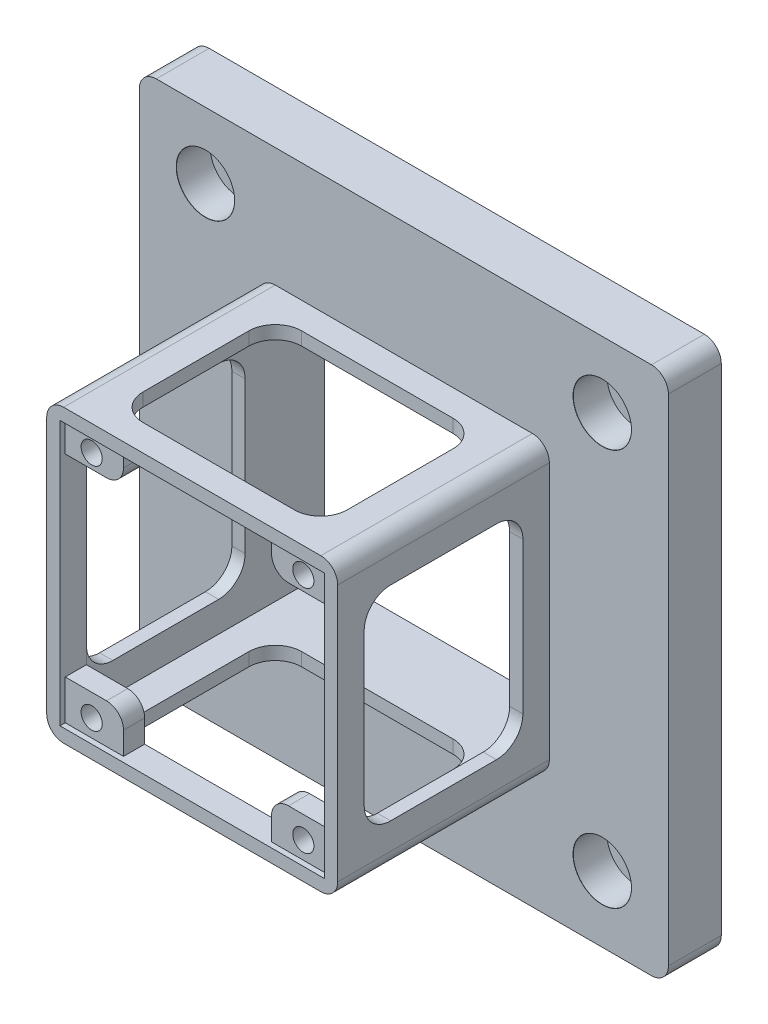
SolidWorks part; units mm, degrees
ref_plane "Front Plane" through (0, 0, 0) normal (1, 0, 0) x (0, 1, 0)
ref_plane "Top Plane" through (0, 0, 0) normal (0, 0, 1) x (0, 1, 0)
ref_plane "Right Plane" through (0, 0, 0) normal (0, 1, 0) x (-1, 0, 0)
sketch "Sketch2" plane through (0, 0, 0) normal (0, 0, 1) x (0, 1, 0)
  line L0 (25, 25) -> (50, 50)
  line L1 (-50, 50) -> (50, 50)
  line L2 (-50, 50) -> (-50, -50)
  line L3 (-50, -50) -> (50, -50)
  line L4 (50, 50) -> (50, -50)
  line L5 (-50, 50) -> (50, -50) construction
  line L6 (-50, -50) -> (50, 50) construction
  line L7 (-25, -25) -> (25, -25)
  line L8 (-25, -25) -> (-25, 25)
  line L9 (-25, 25) -> (25, 25)
  line L10 (25, -25) -> (25, 25)
  line L11 (-25, -25) -> (25, 25) construction
  line L12 (-25, 25) -> (25, -25) construction
  line L13 (25, -25) -> (50, -50)
  line L14 (37.5, 37.5) -> (37.5, -37.5)
  line L15 (37.5, -37.5) -> (37.5, -50)
  point P0 (0, 0)
  point P6 (0, 0)
  dimension "D1" = 50
  dimension "D2" = 100
extrude "Boss-Extrude1" add sketch "Sketch2" along normal blind 10 contours L7 L10 L9 L8 | L8 L7 L10 L9 | L2 L1 L4 L3 region at (0, 0, 0)
sketch "Sketch5" plane through (0, 0, 10) normal (0, 0, 1) x (1, 0, 0)
  line L0 (-37.5, 37.5) -> (37.5, 37.5)
  line L2 (5.5, 0) -> (-5.5, 0) construction
  point P0 (-37.5, 37.5)
  point P1 (37.5, 37.5)
  point P13 (37.5, -37.5)
  point P14 (-37.5, -37.5)
hole_wizard "CBORE for M6 Hex Socket Head Cap Screw1" positions "Sketch5" profile "Sketch6" counterbore size "M6" standard "ISO" end condition through all
sketch "Sketch6" plane through (-37.5, 37.5, 10) normal (1, 0, 0) x (0, -1, 0)
  line L0 (0, 0) -> (0, 10)
  line L1 (0, 10) -> (3.3, 10)
  line L3 (3.3, 10) -> (3.3, 6.4)
  line L4 (5.5, 6.4) -> (3.3, 6.4)
  line L5 (5.5, 6.4) -> (5.5, 0.025)
  line L6 (5.5, 0.025) -> (5.525, 0)
  line L7 (5.525, 0) -> (0, 0)
  line L8 (-5.5, 0.025) -> (-5.525, 0) construction
  line L11 (0, -6.35) -> (0, 107.95) construction
  dimension "Thru Hole Dia." = 6.6
  dimension "Thru Hole Depth" = 10
  dimension "C'Bore Dia." = 11
  dimension "C'Bore Depth" = 6.4
  dimension "Near C'Sink Dia." = 11.05
  dimension "Near C'Sink Angle" = 90
sketch "Sketch7" plane through (0, 0, 10) normal (0, 0, 1) x (1, 0, 0)
  line L0 (25, 25) -> (50, 50) construction
  line L1 (-27.5, -27.5) -> (27.5, -27.5)
  line L2 (-27.5, -27.5) -> (-27.5, 27.5)
  line L3 (-27.5, 27.5) -> (27.5, 27.5)
  line L4 (27.5, -27.5) -> (27.5, 27.5)
  line L5 (-27.5, -27.5) -> (27.5, 27.5) construction
  line L6 (-27.5, 27.5) -> (27.5, -27.5) construction
  point P0 (0, 0)
  line M13 (25, 25) -> (25, -25)
  line M14 (25, -25) -> (-25, -25)
  line M15 (-25, -25) -> (-25, 25)
  line M16 (-25, 25) -> (25, 25)
  dimension "D1" = 55
extrude "Boss-Extrude2" add sketch "Sketch7" along normal blind 40 contours L1 L4 L3 L2 M16 M13 M14 M15 region at (-26.7222, 0, 10)
sketch "Sketch8" plane through (0, 0, 50) normal (0, 0, 1) x (1, 0, 0)
  line L0 (-50, -50) -> (50, 50) construction
  line L5 (-24.7015, -24.7015) -> (24.7015, 24.7015) construction
  line L7 (25, -25) -> (25, 25) construction
  line L8 (-25, 25) -> (25, 25)
  line L9 (-25, 25) -> (-25, 19)
  line L10 (-25, 19) -> (-13.9912, 19)
  line L11 (25, 25) -> (25, 19)
  line L12 (-13.9912, -17.5) -> (-25, -17.5)
  line L13 (-25, 25) -> (-13.9912, 25)
  line L14 (-25, -25) -> (25, -25)
  line L15 (-25, -25) -> (-25, -15)
  line L17 (25, -25) -> (25, -15)
  line L18 (-19.721, 19.721) -> (24.7015, -24.7015) construction
  line L19 (13.9912, 19) -> (25, 19)
  line L20 (-13.9912, -25) -> (-13.9912, -17.5)
  line L21 (13.9912, -25) -> (-13.9912, -25)
  line L22 (13.9912, -25) -> (13.9912, -17.5)
  line L24 (0, -25) -> (0, -24.7015)
  line L27 (13.9912, 19) -> (13.9912, 25)
  line L28 (13.9912, 25) -> (-13.9912, 25)
  line L29 (-13.9912, 19) -> (-13.9912, 25)
  line L30 (25, -17.5) -> (13.9912, -17.5)
  line L31 (-25, 25) -> (-25, 19)
  line L32 (-25, 19) -> (-13.9912, 19)
  line L33 (-13.9912, 25) -> (-13.9912, 19)
  line L34 (13.9912, 25) -> (25, 25)
  line L35 (13.9912, 25) -> (13.9912, 19)
  line L36 (13.9912, 19) -> (25, 19)
  line L37 (25, 25) -> (25, 19)
  line L38 (13.9912, -17.5) -> (25, -17.5)
  line L39 (13.9912, -17.5) -> (13.9912, -25)
  line L40 (13.9912, -25) -> (25, -25)
  line L41 (25, -17.5) -> (25, -25)
  line L42 (-25, -17.5) -> (-13.9912, -17.5)
  line L43 (-25, -17.5) -> (-25, -25)
  line L44 (-25, -25) -> (-13.9912, -25)
  line L45 (-13.9912, -17.5) -> (-13.9912, -25)
  circle A0 centre (-20, 21.7015) radius 2
  circle A1 centre (20, 21.7015) radius 2
  circle A2 centre (20, -21.7015) radius 2
  circle A3 centre (-20, -21.7015) radius 2
  point P0 (0, 0)
  line M10 (-25, 25) -> (25, 25)
  line M11 (25, 25) -> (25, -25)
  line M12 (25, -25) -> (-25, -25)
  line M13 (-25, -25) -> (-25, 25)
  dimension "D5" = 4
  dimension "D8" = 4
  dimension "D1" = 49.403
  dimension "D2" = 6
  dimension "D3" = 10
  dimension "D4" = 40
  dimension "D7" = 40
other "AlignGroup1"
extrude "Boss-Extrude3" add sketch "Sketch8" against normal blind 5 contours L10 L29 A0 M10 M13 | L27 L19 A1 M11 M10 | L17 L30 L22 A2 M12 | L14 L20 L12 A3 M13 region at (-19.4956, 24.8746, 50) region at (19.4956, 24.8746, 50) region at (-19.4956, -17.6332, 50) region at (24.8668, -21.25, 50)
sketch "Sketch9" plane through (0, 0, 50) normal (0, 0, 1) x (1, 0, 0)
  line L1 (-25, -17.5) -> (-13.9912, -17.5)
  line L2 (-25, -17.5) -> (-25, -25)
  line L3 (-25, -25) -> (-13.9912, -25)
  line L4 (-13.9912, -17.5) -> (-13.9912, -25)
  line L5 (13.9912, -17.5) -> (25, -17.5)
  line L6 (13.9912, -17.5) -> (13.9912, -25)
  line L7 (13.9912, -25) -> (25, -25)
  line L8 (25, -17.5) -> (25, -25)
  line L9 (13.9912, 25) -> (25, 25)
  line L10 (13.9912, 25) -> (13.9912, 19)
  line L11 (13.9912, 19) -> (25, 19)
  line L12 (25, 25) -> (25, 19)
  line L13 (-25, 25) -> (-13.9912, 25)
  line L14 (-25, 25) -> (-25, 19)
  line L15 (-25, 19) -> (-13.9912, 19)
  line L16 (-13.9912, 25) -> (-13.9912, 19)
  circle A0 centre (-20, -21.7015) radius 2
extrude "Cut-Extrude1" cut sketch "Sketch9" against normal blind 1
fillet "Fillet1" radius 3.2 12 edges at (13.9912, 19, 47) (-13.9912, 19, 47) (13.9912, -17.5, 47) (-13.9912, -17.5, 47) (-27.5, -27.5, 30) (-50, -50, 5) (27.5, -27.5, 30) (50, -50, 5) (50, 50, 5) (27.5, 27.5, 30) (-50, 50, 5) (-27.5, 27.5, 30)
sketch "Sketch10" plane through (0, 0, 49) normal (0, 0, 1) x (1, 0, 0)
  point P0 (-20, -21.7015)
  point P1 (-20, 21.7015)
  point P3 (20, 21.7015)
  point P5 (20, -21.7015)
sketch "Sketch11" plane through (-27.5, 0, 0) normal (-1, 0, 0) x (0, -1, 0)
  line L1 (-19.3, 15) -> (19.3, 15)
  line L2 (19.3, 15) -> (19.3, 45)
  line L3 (19.3, 45) -> (-19.3, 45)
  line L4 (-19.3, 45) -> (-19.3, 15)
  line L5 (-24.3, 10) -> (24.3, 10)
  line L6 (24.3, 10) -> (24.3, 50)
  line L7 (24.3, 50) -> (-24.3, 50)
  line L8 (-24.3, 50) -> (-24.3, 10)
  line L9 (-24.3, 10) -> (24.3, 10)
  line L10 (24.3, 10) -> (24.3, 50)
  line L11 (24.3, 50) -> (-24.3, 50)
  line L12 (-24.3, 50) -> (-24.3, 10)
  line L13 (-24.3, 15) -> (24.3, 15)
  dimension "D3" = 5
  dimension "D1" = 0
  dimension "D2" = 5
extrude "Cut-Extrude2" cut sketch "Sketch11" against normal through all contours L3 L4 L1 L2 region at (-27.5, 0, 30)
sketch "Sketch12" plane through (0, -27.5, 0) normal (0, -1, 0) x (1, 0, 0)
  line L0 (19.3, 45) -> (-19.3, 45)
  line L1 (-19.3, 45) -> (-19.3, 15)
  line L2 (-19.3, 15) -> (19.3, 15)
  line L3 (19.3, 15) -> (19.3, 45)
  line L4 (24.3, 50) -> (-24.3, 50)
  line L5 (-24.3, 50) -> (-24.3, 10)
  line L6 (-24.3, 10) -> (24.3, 10)
  line L7 (24.3, 10) -> (24.3, 50)
  line L8 (24.3, 50) -> (-24.3, 50)
  line L9 (-24.3, 50) -> (-24.3, 10)
  line L10 (-24.3, 10) -> (24.3, 10)
  line L11 (24.3, 10) -> (24.3, 50)
  dimension "D1" = 0
  dimension "D2" = 5
extrude "Cut-Extrude3" cut sketch "Sketch12" against normal through all contours L0 L1 L2 L3
fillet "Fillet3" radius 5 12 edges at (-19.3, -26.25, 45) (-19.3, -26.25, 15) (-26.25, -19.3, 45) (-26.25, -19.3, 15) (-19.3, 26.25, 15) (-19.3, 26.25, 45) (19.3, 26.25, 15) (19.3, 26.25, 45) (26.25, -19.3, 45) (26.25, 19.3, 45) (26.25, 19.3, 15) (26.25, -19.3, 15)
fillet "Fillet4" radius 5 4 edges at (-26.25, 19.3, 45) (-26.25, 19.3, 15) (19.3, -26.25, 15) (19.3, -26.25, 45)
